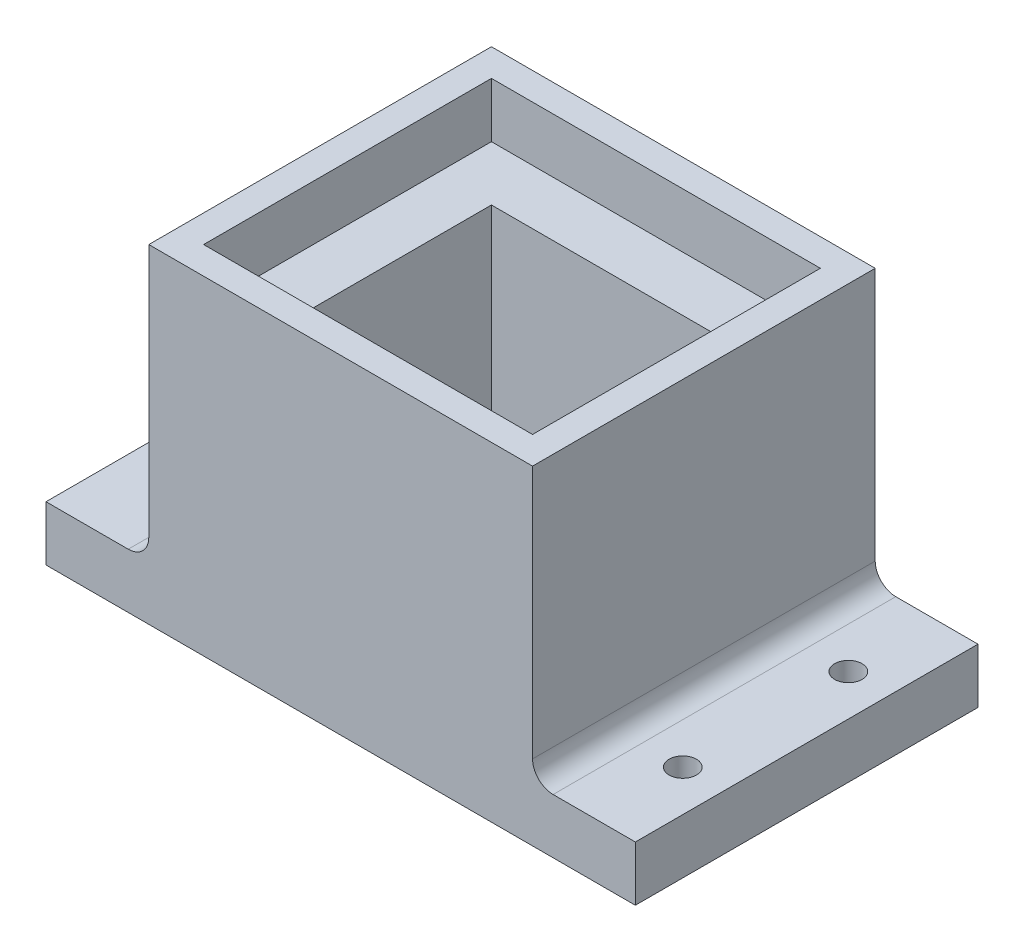
SolidWorks part; units mm, degrees
ref_plane "Front Plane" through (0, 0, 0) normal (0, 0, 1) x (1, 0, 0)
ref_plane "Top Plane" through (0, 0, 0) normal (0, 1, 0) x (1, 0, 0)
ref_plane "Right Plane" through (0, 0, 0) normal (1, 0, 0) x (0, 0, -1)
sketch "Sketch1" plane through (0, 0, 0) normal (0, 1, 0) x (1, 0, 0)
  line L1 (-28, -25) -> (28, -25)
  line L2 (-28, -25) -> (-28, 25)
  line L3 (-28, 25) -> (28, 25)
  line L4 (28, -25) -> (28, 25)
  line L5 (-28, -25) -> (28, 25) construction
  line L6 (-28, 25) -> (28, -25) construction
  point P0 (0, 0)
  dimension "D1" = 50
  dimension "D2" = 56
extrude "Boss-Extrude1" add sketch "Sketch1" along normal blind 48
sketch "Sketch3" plane through (0, 48, 0) normal (0, 1, 0) x (1, 0, 0)
  line L0 (28, 25) -> (-28, 25) construction
  line L1 (-24, -21) -> (24, -21)
  line L2 (-24, -21) -> (-24, 21)
  line L3 (-24, 21) -> (24, 21)
  line L4 (24, -21) -> (24, 21)
  line L5 (-24, -21) -> (24, 21) construction
  line L6 (-24, 21) -> (24, -21) construction
  line L7 (28, -25) -> (28, 25) construction
  point P0 (0, 0)
  dimension "D1" = 4
  dimension "D2" = 4
extrude "Cut-Extrude1" cut sketch "Sketch3" against normal blind 8
sketch "Sketch4" plane through (0, 0, 25) normal (0, 0, 1) x (1, 0, 0)
  line L1 (-28, 0) -> (-43, 0)
  line L2 (-28, 0) -> (-28, 8)
  line L3 (-28, 8) -> (-43, 8)
  line L4 (-43, 0) -> (-43, 8)
  line L5 (28, 0) -> (43, 0)
  line L6 (28, 0) -> (28, 8)
  line L7 (28, 8) -> (43, 8)
  line L8 (43, 0) -> (43, 8)
  dimension "D1" = 8
  dimension "D2" = 15
extrude "Boss-Extrude2" add sketch "Sketch4" against normal up to surface (50 mm away) up to face at (0, 24, -25)
fillet "Fillet1" radius 3 2 edges at (28, 8, 0) (-28, 8, 0)
sketch "Sketch5" plane through (0, 40, 0) normal (0, 1, 0) x (1, 0, 0)
  line L0 (-24, 21) -> (-24, -21) construction
  line L1 (-16, -13) -> (16, -13)
  line L2 (-16, -13) -> (-16, 13)
  line L3 (-16, 13) -> (16, 13)
  line L4 (16, -13) -> (16, 13)
  line L5 (-16, -13) -> (16, 13) construction
  line L6 (-16, 13) -> (16, -13) construction
  line L7 (24, 21) -> (-24, 21) construction
  point P0 (0, 0)
  dimension "D1" = 8
  dimension "D2" = 8
extrude "Cut-Extrude2" cut sketch "Sketch5" against normal through all both and the other way through all
sketch "Sketch6" plane through (0, 8, 0) normal (0, 1, 0) x (1, 0, 0)
  line L0 (-37, 25) -> (-37, -25) construction
  line L1 (-43, 25) -> (-31, 25) construction
  line L2 (-31, -25) -> (-43, -25) construction
  line L3 (-37, -12.0794) -> (-37, -25) construction
  line L4 (-37, 12.0794) -> (-37, 25) construction
  line L5 (0, 13) -> (0, -13) construction
  line L6 (-16, 13) -> (16, 13) construction
  line L7 (16, -13) -> (-16, -13) construction
  circle A0 centre (-37, 12.0794) radius 2
  circle A1 centre (-37, -12.0794) radius 2
  circle A2 centre (37, -12.0794) radius 2
  circle A3 centre (37, 12.0794) radius 2
  dimension "D1" = 4
  dimension "D2" = 4
  dimension "D3" = 12.9206
extrude "Cut-Extrude3" cut sketch "Sketch6" against normal through all both
